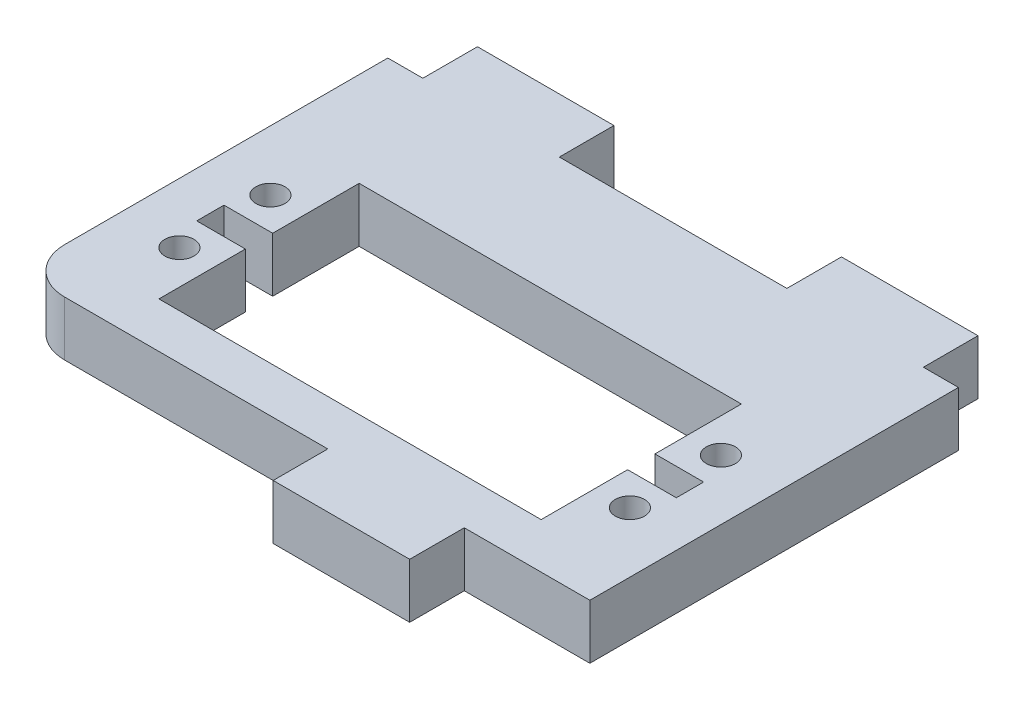
SolidWorks part; units mm, degrees
material "MDF"
ref_plane "Plano frontal" through (0, 0, 0) normal (0, 0, 1) x (1, 0, 0)
ref_plane "Plano superior" through (0, 0, 0) normal (0, 1, 0) x (1, 0, 0)
ref_plane "Plano direito" through (0, 0, 0) normal (1, 0, 0) x (0, 0, -1)
ref_plane "Plano1" through (0, -6, 0) normal (0, -1, 0) x (1, 0, 0)
sketch "Esboço1" plane through (0, -6, 0) normal (0, -1, 0) x (1, 0, 0)
  line L0 (-26.35, 1.5) -> (-21, 1.5)
  line L1 (-21, 1.5) -> (-21, 11)
  line L2 (-21, 11) -> (21, 11)
  line L3 (21, 11) -> (21, 1.5)
  line L4 (21, 1.5) -> (26.35, 1.5)
  line L5 (26.35, 1.5) -> (26.35, -1.5)
  line L6 (26.35, -1.5) -> (21, -1.5)
  line L7 (21, -1.5) -> (21, -11)
  line L8 (21, -11) -> (-21, -11)
  line L9 (-21, -11) -> (-21, -1.5)
  line L10 (-21, -1.5) -> (-26.35, -1.5)
  line L11 (-26.35, -1.5) -> (-26.35, 1.5)
  line L12 (2.5526, 16) -> (-26.35, 16)
  line L13 (-31.35, 11) -> (-31.35, -24.5)
  line L14 (-31.35, -24.5) -> (-27.5, -24.5)
  line L15 (-27.5, -24.5) -> (-27.5, -30.5)
  line L16 (-27.5, -30.5) -> (-12.5, -30.5)
  line L17 (-12.5, -30.5) -> (-12.5, -24.5)
  line L18 (-12.5, -24.5) -> (12.5, -24.5)
  line L19 (12.5, -24.5) -> (12.5, -30.5)
  line L20 (12.5, -30.5) -> (27.5, -30.5)
  line L21 (27.5, -30.5) -> (27.5, -24.5)
  line L22 (27.5, -24.5) -> (31.35, -24.5)
  line L23 (31.35, -24.5) -> (31.35, 16)
  line L24 (31.35, 16) -> (17.5526, 16)
  line L25 (17.5526, 16) -> (17.5526, 22)
  line L26 (17.5526, 22) -> (2.5526, 22)
  line L27 (2.5526, 22) -> (2.5526, 16)
  line L28 (-24.75, 5) -> (24.75, -5) construction
  line L29 (21, 11) -> (-21, -11) construction
  circle A0 centre (24.75, 5) radius 1.6
  circle A1 centre (24.75, -5) radius 1.6
  circle A2 centre (-24.75, 5) radius 1.6
  circle A3 centre (-24.75, -5) radius 1.6
  arc A4 (-26.35, 16) -> (-31.35, 11) centre (-26.35, 11) ccw
  point P38 (0, 0)
  point P46 (0, -24.5)
  point P50 (10.0526, 22)
  point P53 (26.35, 0)
  point P54 (-26.35, 0)
  dimension "D10" = 3.2
  dimension "D11" = 6.6
  dimension "D13" = 5
  dimension "D1" = 40.5
  dimension "D2" = 62.7
  dimension "D3" = 6
  dimension "D4" = 25
  dimension "D5" = 42
  dimension "D6" = 22
  dimension "D7" = 49.5
  dimension "D8" = 10
  dimension "D9" = 15
  dimension "D12" = 5
  dimension "D14" = 10.0526
  dimension "D15" = 3
  dimension "D16" = 1.6
extrude "Ressalto-extrusão1" add sketch "Esboço1" against normal blind 6
